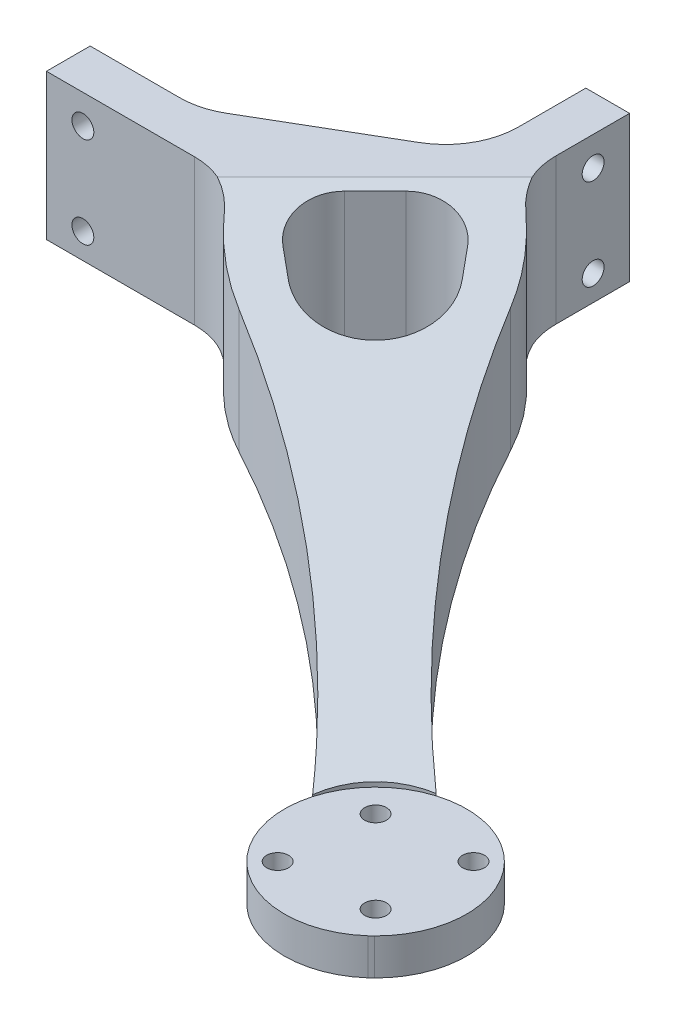
SolidWorks part; units mm, degrees
ref_plane "Front Plane" through (0, 0, 0) normal (0, 0, 1) x (1, 0, 0)
ref_plane "Top Plane" through (0, 0, 0) normal (0, 1, 0) x (1, 0, 0)
ref_plane "Right Plane" through (0, 0, 0) normal (1, 0, 0) x (0, 0, -1)
sketch "Sketch1" plane through (0, 0, 0) normal (0, 1, 0) x (1, 0, 0)
  line L0 (-32.8333, 3.1667) -> (-17.8333, 3.1667)
  line L1 (-17.8333, 3.1667) -> (7.1667, 18.1667)
  line L2 (7.1667, 18.1667) -> (7.1667, 33.1667)
  line L3 (7.1667, 33.1667) -> (12.1667, 33.1667)
  line L4 (12.1667, 33.1667) -> (12.1667, 18.1667)
  line L8 (-7.8333, -1.8333) -> (-32.8333, -1.8333)
  line L9 (-32.8333, -1.8333) -> (-32.8333, 3.1667)
  line L11 (12.1667, 18.1667) -> (17.5272, 18.1667)
  line L12 (-7.8333, -1.8333) -> (-7.8333, -7.1938)
  arc A0 (56.4946, -55.8323) -> (66.1657, -46.1613) centre (65.8063, -55.4729) ccw
  arc A1 (56.4946, -55.8323) -> (-7.8333, -7.1938) centre (-62.8059, -146.7575) ccw
  arc A2 (17.5272, 18.1667) -> (66.1657, -46.1613) centre (157.0908, 73.1392) ccw
  dimension "D1" = 15
  dimension "D2" = 5
  dimension "D3" = 15
  dimension "D4" = 5
  dimension "D5" = 25
  dimension "D6" = 25
  dimension "D7" = 15
  dimension "D8" = 15
  dimension "D11" = 155
  dimension "D14" = 155
extrude "Boss-Extrude3" add sketch "Sketch1" along normal blind 25
chamfer "Chamfer2" distance 6 angle 33 2 edges at (-7.8333, 12.5, 7.1938) (17.5272, 12.5, -18.1667) first distance on face at (-7.8333, 12.5, 4.5136) first distance on face at (39.6443, 12.5, 15.6623)
fillet "Fillet2" radius 30 2 edges at (19.7268, 12.5, -12.8805) (-2.8836, 12.5, 9.2464)
sketch "Sketch4" plane through (0, 25, 0) normal (0, 1, 0) x (1, 0, 0)
  line L0 (17.1652, 5.2091) -> (10.4484, 13.8698)
  line L1 (10.4484, 13.8698) -> (-3.4214, 0)
  line L2 (-3.4214, 0) -> (5.2393, -6.7168)
  arc A0 (56.4946, -55.8323) -> (4.4419, -12.6764) centre (-62.8059, -146.7575) ccw construction
  arc A1 (22.8804, 6.15) -> (66.1657, -46.1613) centre (157.0908, 73.1392) ccw construction
  arc A2 (22.8804, 6.15) -> (66.1657, -46.1613) centre (157.0908, 73.1392) ccw construction
  arc A4 (5.2393, -6.7168) -> (17.1652, 5.2091) centre (10.4484, 0) ccw
extrude "Cut-Extrude4" cut sketch "Sketch4" against normal blind 25
fillet "Fillet3" radius 6 2 edges at (10.4484, 12.5, -13.8698) (-3.4214, 12.5, 0)
sketch "Sketch7" plane through (0, 25, 0) normal (0, 1, 0) x (1, 0, 0)
  line L0 (8.9535, 27.4642) -> (42.7588, -6.3411)
  line L1 (42.7588, -6.3411) -> (46.7756, -2.3243)
  line L2 (46.7756, -2.3243) -> (12.9703, 31.481)
  line L3 (12.9703, 31.481) -> (8.9535, 27.4642)
extrude "Boss-Extrude4" add sketch "Sketch7" along normal blind 25
sketch "Sketch10" plane through (22.2256, 0, -22.2256) normal (0.7071, 0, -0.7071) x (-0.7071, 0, -0.7071)
  line L0 (-95.076, 0) -> (-95.076, 5)
  line L1 (-95.076, 25) -> (-95.076, 0) construction
  line L2 (-95.076, 5) -> (-72.576, 5)
  line L3 (-72.576, 5) -> (4.1734, 25)
  line L4 (4.1734, 25) -> (18.3848, 25)
  line L5 (18.3848, 25) -> (25.4558, 25)
  line L6 (18.3848, 25) -> (18.3848, 0) construction
  line L7 (18.3848, 5) -> (4.1734, 5)
  line L8 (4.1734, 25) -> (4.1734, 0) construction
  line L9 (4.1734, 5) -> (-65.076, 0)
  line L10 (-79.4271, 0) -> (-11.8302, 0) construction
  line L11 (-65.076, 0) -> (-95.076, 0)
  line L12 (25.4558, 25) -> (25.4558, 5)
  line L13 (-116.8035, -30.6808) -> (43.3804, -30.6808)
  line L14 (-116.8035, -30.6808) -> (-116.8035, 52.4335)
  line L15 (-116.8035, 52.4335) -> (43.3804, 52.4335)
  line L16 (43.3804, -30.6808) -> (43.3804, 52.4335)
  line L17 (25.4558, 25) -> (25.4558, 0) construction
  line L18 (25.4558, 5) -> (18.3848, 5)
  dimension "D1" = 22.5
  dimension "D2" = 30
  dimension "D3" = 5
  dimension "D4" = 20
extrude "Cut-Extrude6" cut sketch "Sketch10" against normal blind 100 and the other way blind 100
sketch "Sketch11" plane through (0, 5, 0) normal (0, 1, 0) x (1, 0, 0)
  circle A0 centre (63.6345, -53.1462) radius 12.5
  arc A1 (56.4946, -55.8323) -> (66.1657, -46.1613) centre (65.8063, -55.4729) ccw construction
  point P2 (72.3955, -62.0622)
  dimension "D1" = 12.5
extrude "Boss-Extrude5" add sketch "Sketch11" against normal up to surface (5 mm away) up to face at (59.0278, 0, 48.6945)
sketch "Sketch12" plane through (0, 5, 0) normal (0, 1, 0) x (1, 0, 0)
  circle A0 centre (63.6345, -53.1462) radius 12.5
extrude "Cut-Extrude7" cut sketch "Sketch12" along normal blind 100
sketch "Sketch14" plane through (7.1667, 0, 0) normal (-1, 0, 0) x (0, 0, 1)
  line L0 (-33.1667, 25) -> (-33.1667, 5) construction
  line L1 (-33.1667, 25) -> (-18.1667, 25) construction
  circle A0 centre (-28.1667, 21) radius 1.5
  circle A1 centre (-28.1667, 8.5) radius 1.5
  point P4 (-25.6667, 25)
  dimension "D1" = 5
  dimension "D3" = 12.5
  dimension "D2" = 4
extrude "Cut-Extrude8" cut sketch "Sketch14" against normal blind 10
sketch "Sketch15" plane through (0, 0, -3.1667) normal (0, 0, -1) x (-1, 0, 0)
  line L0 (17.8333, 25) -> (32.8333, 25) construction
  line L1 (32.8333, 25) -> (32.8333, 5) construction
  circle A0 centre (27.8333, 21) radius 1.5
  circle A1 centre (27.8333, 8.5) radius 1.5
  dimension "D1" = 4
  dimension "D3" = 12.5
  dimension "D2" = 5
extrude "Cut-Extrude9" cut sketch "Sketch15" against normal blind 10
fillet "Fillet6" radius 10 2 edges at (-7.5027, 14.9726, 1.8333) (12.1667, 15, -18.0687)
sketch "Sketch16" plane through (0, 5, 0) normal (0, 1, 0) x (1, 0, 0)
  circle A0 centre (70.352, -46.4287) radius 1.5
  circle A1 centre (57.9776, -47.4894) radius 1.5
  circle A2 centre (56.917, -59.8637) radius 1.5
  circle A3 centre (69.2914, -58.8031) radius 1.5
  dimension "D3" = 19
  dimension "D4" = 16
extrude "Cut-Extrude10" cut sketch "Sketch16" against normal blind 10
sketch "Sketch17" plane through (0, 0, 0) normal (0, -1, 0) x (1, 0, 0)
  line L2 (67.17, 54.5604) -> (62.2203, 49.6107)
  line L5 (60.099, 51.732) -> (65.0487, 56.6818)
  line L6 (68.2307, 59.8637) -> (69.2914, 58.8031)
  line L7 (62.2203, 49.6107) -> (60.099, 51.732)
  line L8 (60.099, 51.732) -> (65.0487, 56.6818)
  line L9 (65.0487, 56.6818) -> (67.17, 54.5604)
  line L10 (67.17, 54.5604) -> (62.2203, 49.6107)
  circle A0 centre (69.2914, 58.8031) radius 1.5 construction
  dimension "D2" = 3
  dimension "D3" = 7
extrude "Boss-Extrude7" add sketch "Sketch17" along normal blind 7 contours L9 L5 L7 L2 region at (63.6345, 0, 53.1462)
sketch "Sketch19" plane through (6.3048, 0, -6.3048) normal (0.7071, 0, -0.7071) x (-0.7071, 0, -0.7071)
  line L0 (-86.0764, -7) -> (-79.0764, -7) construction
  line L1 (-79.0764, -7) -> (-79.0764, 0) construction
  circle A0 centre (-82.5764, -3.5) radius 1.5
  dimension "D1" = 3.5
  dimension "D2" = 3.5
extrude "Cut-Extrude12" cut sketch "Sketch19" against normal blind 7
fillet "Fillet7" radius 3.5 2 edges
sketch "Sketch20" plane through (7.1667, 0, 0) normal (-1, 0, 0) x (0, 0, 1)
  line L1 (-33.1667, 5) -> (-18.1667, 5)
  line L2 (-33.1667, 5) -> (-33.1667, 25)
  line L3 (-33.1667, 25) -> (-18.1667, 25)
  line L4 (-18.1667, 5) -> (-18.1667, 25)
  circle A0 centre (-28.1667, 21) radius 1.5
  circle A1 centre (-28.1667, 8.5) radius 1.5
extrude "Boss-Extrude8" add sketch "Sketch20" along normal blind 1
sketch "Sketch21" plane through (0, 0, -3.1667) normal (0, 0, -1) x (-1, 0, 0)
  line L1 (17.8333, 5) -> (32.8333, 5)
  line L2 (17.8333, 5) -> (17.8333, 25)
  line L3 (17.8333, 25) -> (32.8333, 25)
  line L4 (32.8333, 5) -> (32.8333, 25)
  circle A0 centre (27.8333, 21) radius 1.5
  circle A1 centre (27.8333, 8.5) radius 1.5
extrude "Boss-Extrude9" add sketch "Sketch21" along normal blind 1
sketch "Sketch22" plane through (0, 25, 0) normal (0, 1, 0) x (1, 0, 0)
  line L0 (-17.8333, 4.1667) -> (6.1667, 18.1667)
  line L1 (6.1667, 18.1667) -> (7.1667, 18.1667)
  line L2 (7.1667, 18.1667) -> (-16.7108, 1.2718)
  line L3 (-16.7108, 1.2718) -> (-20.3121, 2.4335)
  line L4 (-20.3121, 2.4335) -> (-17.8333, 4.1667)
extrude "Boss-Extrude10" add sketch "Sketch22" against normal up to surface (20 mm away) up to face at (-5.4765, 5, -12.4988)
fillet "Fillet8" radius 10 2 edges at (6.1667, 15, -18.1667) (-17.8333, 15, -4.1667)
